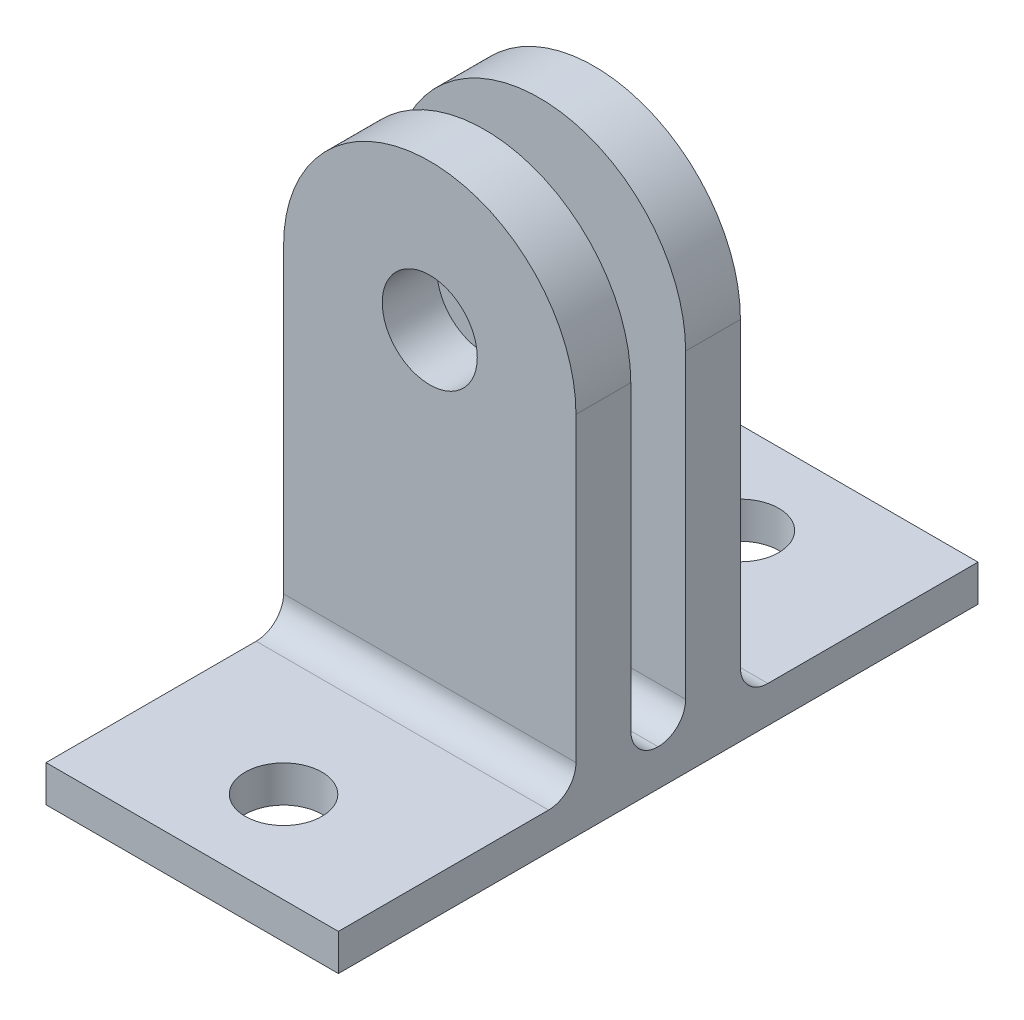
SolidWorks part; units mm, degrees
ref_plane "前基準面" through (0, 0, 0) normal (0, 0, 1) x (1, 0, 0)
ref_plane "上基準面" through (0, 0, 0) normal (0, 1, 0) x (1, 0, 0)
ref_plane "右基準面" through (0, 0, 0) normal (1, 0, 0) x (0, 0, -1)
sketch "草圖2" plane through (0, 0, 0) normal (0, 1, 0) x (1, 0, 0)
  line L0 (-18.1017, 0) -> (18.1017, 0) construction
  line L1 (8, 17.5) -> (8, -17.5)
  line L2 (-8, -17.5) -> (8, -17.5)
  line L3 (-8, -17.5) -> (-8, 17.5)
  line L4 (-8, 17.5) -> (8, 17.5)
  line L5 (8, -17.5) -> (8, 17.5) construction
  line L6 (0, 17.5) -> (0, -17.5) construction
  line L7 (-8, 0) -> (8, 0) construction
  line L9 (8, 17.5) -> (8, -17.5) construction
  point P1 (0, 0)
  point P4 (0, 0)
  dimension "D1" = 16
  dimension "D2" = 35
extrude "填料-伸長1" add sketch "草圖2" along normal blind 2
sketch "草圖4" plane through (0, 0, 0) normal (0, 0, 1) x (1, 0, 0)
  line L0 (0, -10.2424) -> (0, 10.2424) construction
  line L3 (8, 20) -> (-8, 20) construction
  line L4 (8, 20) -> (8, 2)
  line L5 (8, 2) -> (-8, 2)
  line L6 (-8, 20) -> (-8, 2)
  line L7 (0, 2) -> (0, 20) construction
  line L8 (8, 11) -> (-8, 11) construction
  arc A0 (-8, 20) -> (8, 20) centre (0, 20) cw
  circle A1 centre (0, 20) radius 2.6
  point P1 (0, 11)
  point P6 (0, 0)
  dimension "D2" = 5.2
  dimension "D1" = 18
extrude "填料-伸長2" add sketch "草圖4" along normal blind 3 from offset 1.5
mirror "鏡射1" about plane through (0, 0, 0) normal (0, 0, 1) of "填料-伸長2"
fillet "圓角2" radius 1.5 4 edges at (0, 2, -1.5) (0, 2, -4.5) (0, 2, 4.5) (0, 2, 1.5)
sketch "草圖5" plane through (0, 2, 0) normal (0, 1, 0) x (1, 0, 0)
  line L0 (0, 19.0784) -> (0, -19.0784) construction
  line L2 (-23.5425, 0) -> (23.5425, 0) construction
  circle A0 centre (0, -12.5) radius 2.1
  circle A1 centre (0, 12.5) radius 2.1
  point P6 (0, 0)
  point P9 (0, 0)
  dimension "D1" = 4.2
  dimension "D2" = 25
extrude "除料-伸長1" cut sketch "草圖5" against normal through all
